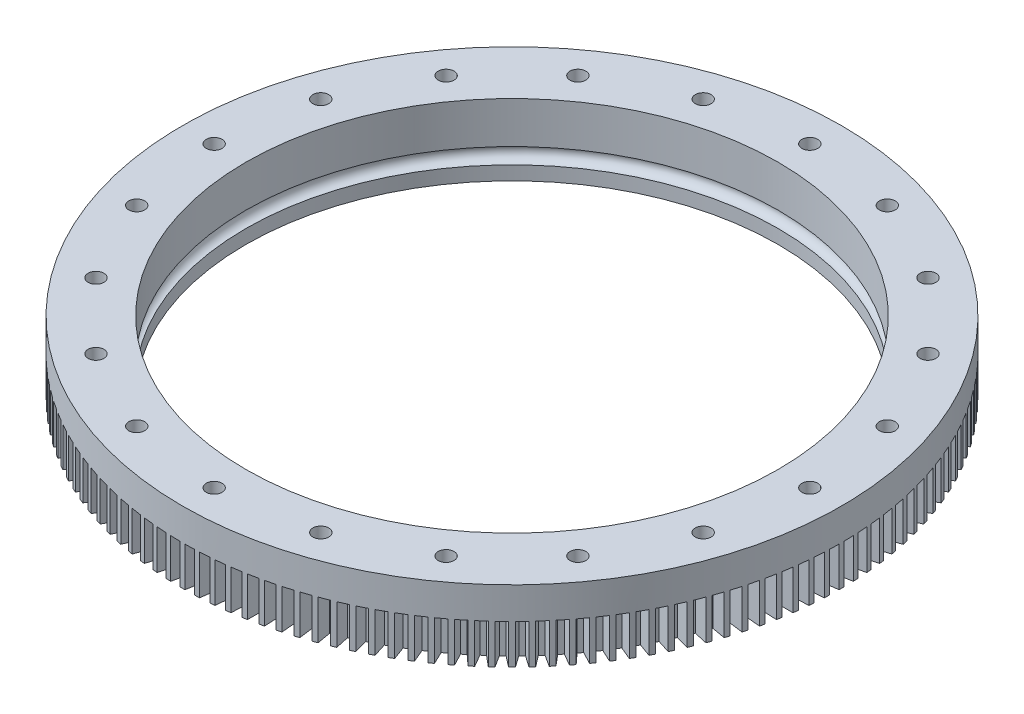
SolidWorks part; units mm, degrees
ref_plane "Plan de face" through (0, 0, 0) normal (0, 0, 1) x (1, 0, 0)
ref_plane "Plan de dessus" through (0, 0, 0) normal (0, 1, 0) x (1, 0, 0)
ref_plane "Plan de droite" through (0, 0, 0) normal (1, 0, 0) x (0, 0, -1)
sketch "Esquisse1" plane through (0, 0, 0) normal (0, 0, 1) x (1, 0, 0)
  line L0 (0, 37.5) -> (0, 90)
  line L1 (0, 0) -> (80, 0)
  line L2 (0, 0) -> (0, 17.5)
  line L3 (0, 90) -> (80, 90)
  line L4 (80, 0) -> (80, 90)
  line L5 (0, 0) -> (-336, 0) construction
  line L6 (-336, 0) -> (-336, 134.4959) construction
  arc A0 (0, 17.5) -> (0, 37.5) centre (0, 27.5) ccw
  dimension "D3" = 10
  dimension "D1" = 80
  dimension "D2" = 90
  dimension "D4" = 62.5
  dimension "D5" = 336
revolve "Révolution1" add sketch "Esquisse1" angle 360 about L6
sketch "Esquisse2" plane through (0, 90, 0) normal (0, 1, 0) x (1, 0, 0)
  circle A0 centre (40, 0) radius 10
  circle A1 centre (-336, 0) radius 336 construction
  dimension "D1" = 376
extrude "Enlèv. mat.-Extru.1" cut sketch "Esquisse2" against normal blind 30
pattern_circular "Répétition circulaire1" count 20 over 360 about axis through (-336, 0, 0) along (0, 1, 0) of "Enlèv. mat.-Extru.1"
sketch "Esquisse3" plane through (0, 0, 0) normal (0, -1, 0) x (1, 0, 0)
  line L0 (-336, 0) -> (80, 0) construction
  line L1 (-336, 0) -> (79.6041, -18.1457) construction
  line L2 (79.9892, -3) -> (62.4297, -6.0962)
  line L3 (62.4297, -6.0962) -> (62.4297, -12.0962)
  line L4 (62.4297, -12.0962) -> (79.7242, -15.1457)
  circle A0 centre (-336, 0) radius 416 construction
  arc A1 (79.7242, -15.1457) -> (79.9892, -3) centre (-336, 0) ccw
  dimension "D1" = 3
  dimension "D2" = 3
  dimension "D3" = 100
  dimension "D4" = 2.5
  dimension "D6" = 100
  dimension "D7" = 6
extrude "Enlèv. mat.-Extru.2" cut sketch "Esquisse3" against normal blind 50
pattern_circular "Répétition circulaire2" count 144 over 360 about axis through (-336, 0, 0) along (0, 1, 0) of "Enlèv. mat.-Extru.2"
